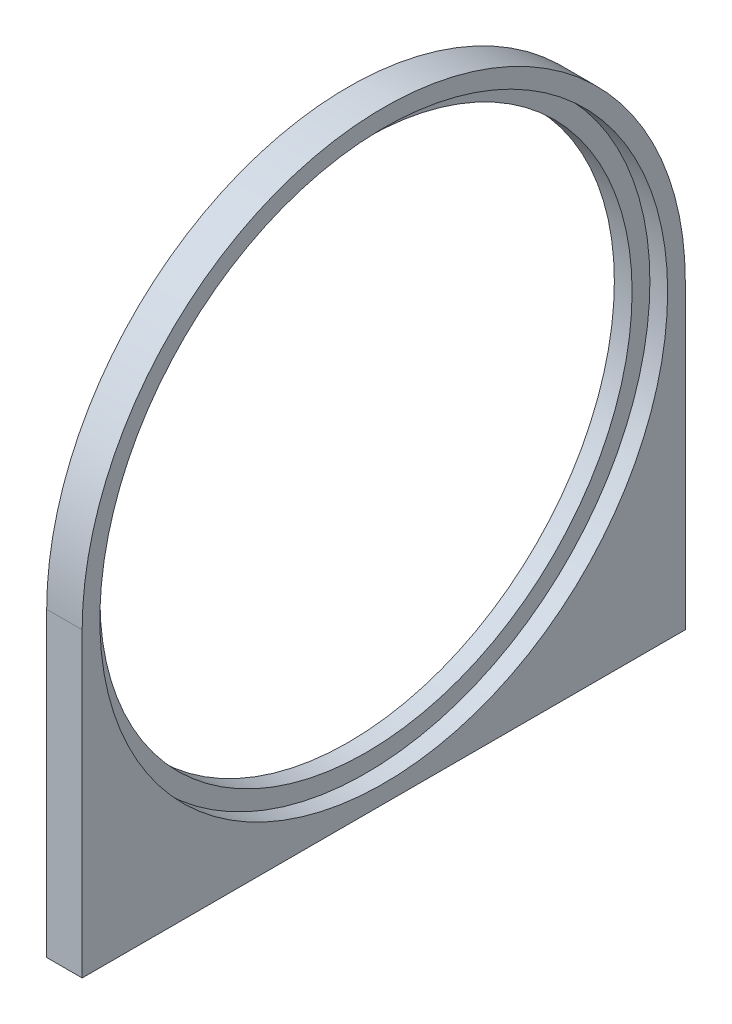
SolidWorks part; units mm, degrees
material "6061-T6 (SS)"
ref_plane "Front" through (0, 0, 0) normal (0, 0, 1) x (1, 0, 0)
ref_plane "Top" through (0, 0, 0) normal (0, 1, 0) x (1, 0, 0)
ref_plane "Right" through (0, 0, 0) normal (1, 0, 0) x (0, 0, -1)
sketch "Sketch1" plane through (0, 0, 0) normal (1, 0, 0) x (0, 0, -1)
  line L0 (-53.975, 0) -> (-53.975, -53.975)
  line L1 (-53.975, -53.975) -> (53.975, -53.975)
  line L2 (53.975, -53.975) -> (53.975, 0)
  arc A0 (53.975, 0) -> (-53.975, 0) centre (0, 0) ccw
  circle A1 centre (0, 0) radius 50.8127
  circle A2 centre (0, 0) radius 47.625
  dimension "D2" = 101.6254
  dimension "D3" = 95.25
  dimension "D1" = 107.95
extrude "Boss-Extrude1" add sketch "Sketch1" along normal blind 6.35 contours L2 A0 L0 L1 A1 region at (0, 52.4484, 0)
extrude "Boss-Extrude2" add sketch "Sketch1<3>" along normal blind 3.175 contours A1 A2 region at (0, 0, 49.3755)
sketch "Sketch1<3>" plane through (0, 0, 0) normal (1, 0, 0) x (0, 0, -1) same geometry as "Sketch1"
hole_wizard "#8-32 Tapped Hole3" positions "Sketch4" profile "Sketch2" tap size "#8-32" standard "ANSI Inch"
sketch "Sketch4" plane through (0, -53.975, 0) normal (0, -1, 0) x (-1, 0, 0)
  line L0 (-3.175, 53.975) -> (-3.175, 44.45) construction
  line L1 (-6.35, 53.975) -> (0, 53.975) construction
  line L2 (-3.175, 44.45) -> (-3.175, 25.4) construction
  line L3 (-3.175, 25.4) -> (-3.175, -25.4) construction
  line L4 (-3.175, -25.4) -> (-3.175, -44.45) construction
  line L5 (-3.175, -44.45) -> (-3.175, -53.975) construction
  line L6 (-6.35, -53.975) -> (0, -53.975) construction
  point P2 (-3.175, 44.45)
  point P5 (-3.175, 25.4)
  point P8 (-3.175, -25.4)
  point P9 (-3.175, -44.45)
  dimension "D1" = 9.525
  dimension "D2" = 19.05
sketch "Sketch2" plane through (3.175, -53.975, -44.45) normal (1, 0, 0) x (0, 0, -1)
  line L0 (0, 0) -> (0, 7.3878)
  line L1 (0, 7.3878) -> (1.7272, 6.35)
  line L2 (1.7272, 6.35) -> (1.7272, 0)
  line L5 (1.7272, 0) -> (0, 0)
  line L10 (0, 7.3878) -> (-1.7272, 6.35) construction
  line L11 (0, -6.35) -> (0, 107.95) construction
  dimension "Tap Drill Dia." = 3.4544
  dimension "Tap Drill Depth" = 6.35
  dimension "Drill Angle" = 118
equation "\"D2@Sketch3\"=2*\"D1@Sketch3\""
equation "\"D2@Sketch4\"=2*\"D1@Sketch4\""
